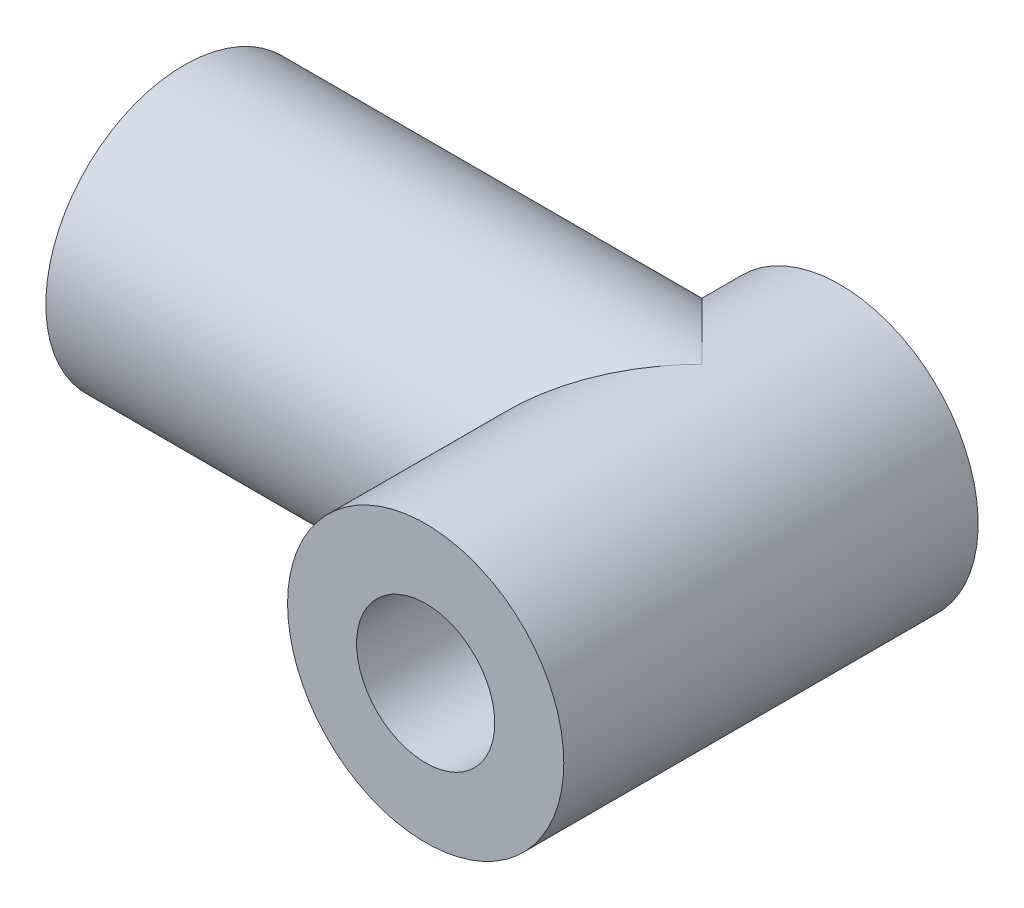
SolidWorks part; units mm, degrees
ref_plane "Front Plane" through (0, 0, 0) normal (0, 0, 1) x (1, 0, 0)
ref_plane "Top Plane" through (0, 0, 0) normal (0, 1, 0) x (1, 0, 0)
ref_plane "Right Plane" through (0, 0, 0) normal (1, 0, 0) x (0, 0, -1)
sketch "Sketch1" plane through (0, 0, 0) normal (0, 0, 1) x (1, 0, 0)
  circle A0 centre (0, 0) radius 2
  circle A1 centre (0, 0) radius 4
  dimension "D1" = 4
  dimension "D2" = 8
extrude "Boss-Extrude1" add sketch "Sketch1" along normal blind 12
sketch "Sketch2" plane through (0, 0, 0) normal (1, 0, 0) x (0, 0, -1)
  line L0 (0, -4) -> (0, 4) construction
  circle A0 centre (-4, 0) radius 2
  circle A1 centre (-4, 0) radius 4
  dimension "D1" = 4
  dimension "D2" = 8
  dimension "D3" = 4
extrude "Boss-Extrude2" add sketch "Sketch2" against normal blind 15
sketch "Sketch3" plane through (0, 0, 0) normal (0, 0, -1) x (-1, 0, 0)
  circle A0 centre (0, 0) radius 2
  circle A1 centre (0, 0) radius 2 construction
extrude "Cut-Extrude1" cut sketch "Sketch3" against normal through all
sketch "Sketch4" plane through (-15, 0, 0) normal (-1, 0, 0) x (0, 0, 1)
  circle A0 centre (4, 0) radius 2
  circle A1 centre (4, 0) radius 2 construction
  point P2 (5.8169, -0.1827)
extrude "Cut-Extrude2" cut sketch "Sketch4" against normal up to surface (15 mm away) up to plane "Right Plane"
